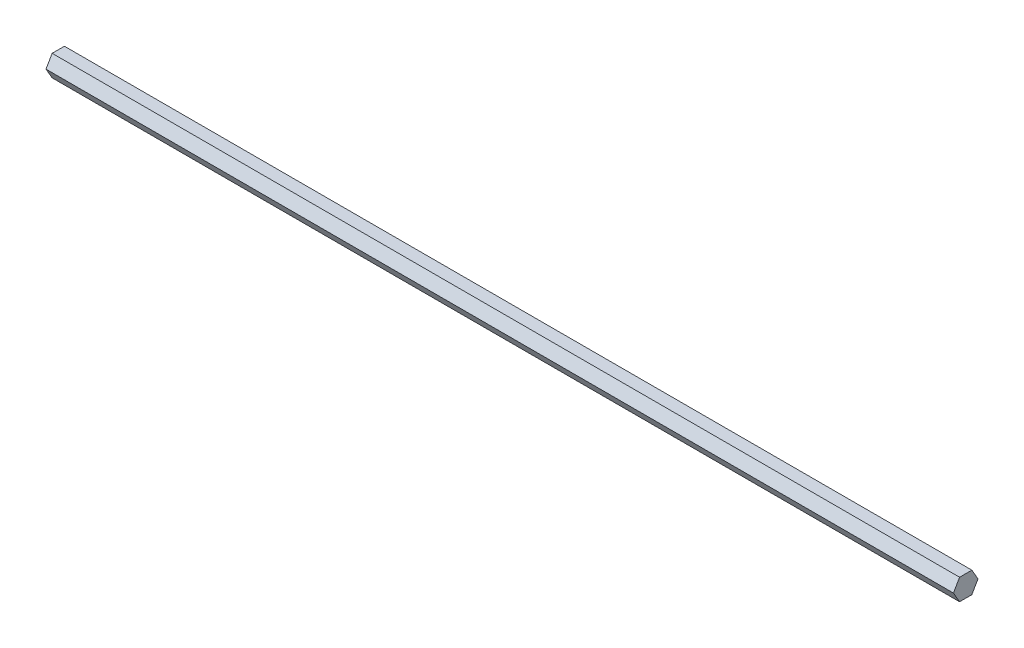
SolidWorks part; units mm, degrees
ref_plane "Front" through (0, 0, 0) normal (0, 0, 1) x (1, 0, 0)
ref_plane "Top" through (0, 0, 0) normal (0, 1, 0) x (1, 0, 0)
ref_plane "Right" through (0, 0, 0) normal (1, 0, 0) x (0, 0, -1)
sketch "Sketch1" plane through (0, 0, 0) normal (1, 0, 0) x (0, 0, -1)
  line L1 (5.4993, 0) -> (2.7496, 4.7625)
  line L2 (2.7496, 4.7625) -> (-2.7496, 4.7625)
  line L3 (-2.7496, 4.7625) -> (-5.4993, 0)
  line L4 (-5.4993, 0) -> (-2.7496, -4.7625)
  line L5 (-2.7496, -4.7625) -> (2.7496, -4.7625)
  line L6 (2.7496, -4.7625) -> (5.4993, 0)
  circle A0 centre (0, 0) radius 4.7625 construction
  dimension "D1" = 9.525
extrude "Boss-Extrude1" add sketch "Sketch1" along normal mid plane 406.4
ref_axis "Axis1" through (-233.7275, 0, 0) along (1, 0, 0)
hole_wizard "1/4-20 Tapped Hole1" positions "Sketch2" profile "Sketch3" tap size "1/4-20" standard "ANSI Inch"
sketch "Sketch2" plane through (-203.2, 0, 0) normal (-1, 0, 0) x (0, 0, 1)
  point P0 (0, 0)
sketch "Sketch3" plane through (-203.2, 0, 0) normal (0, 1, 0) x (0, 0, 1)
  line L0 (0, 0) -> (0, 20.5838)
  line L1 (0, 20.5838) -> (2.5527, 19.05)
  line L2 (2.5527, 19.05) -> (2.5527, 0)
  line L5 (2.5527, 0) -> (0, 0)
  line L10 (0, 20.5838) -> (-2.5527, 19.05) construction
  line L11 (0, -6.35) -> (0, 107.95) construction
  dimension "Tap Drill Dia." = 5.1054
  dimension "Tap Drill Depth" = 19.05
  dimension "Drill Angle" = 118
cosmetic thread "Hole Thread1" parameters "D1"=12.7, "D2"=6.35
